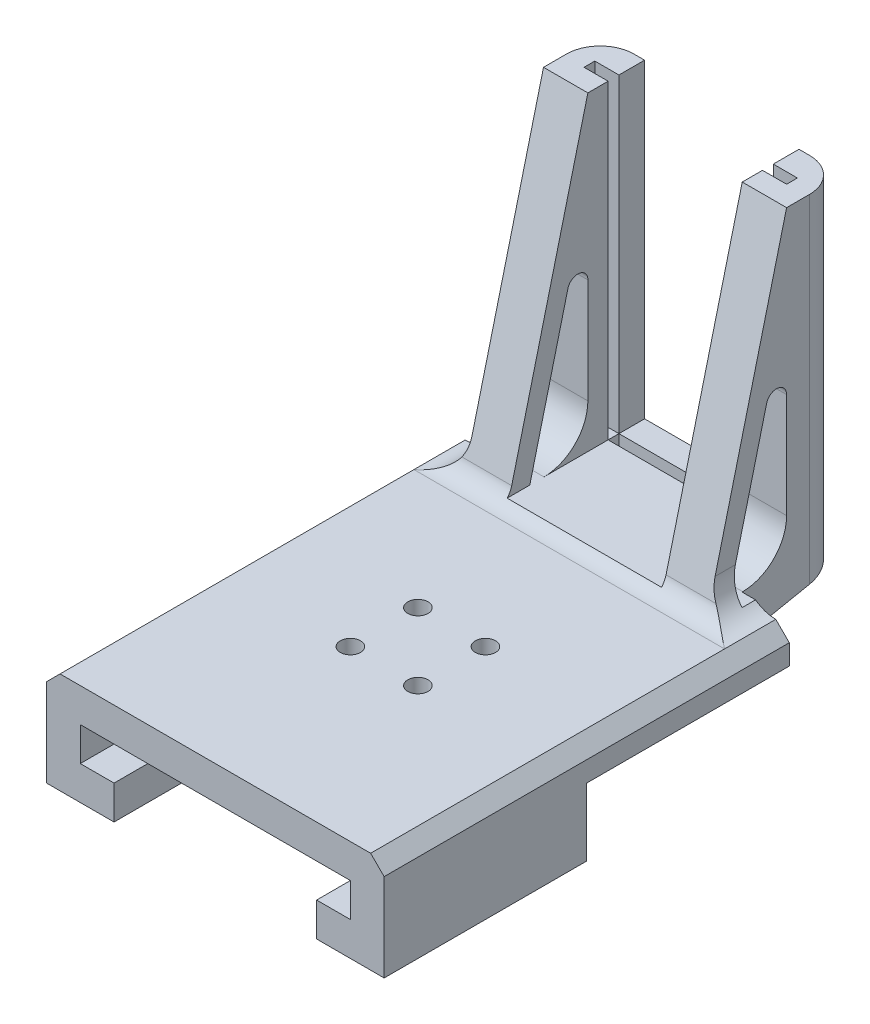
SolidWorks part; units mm, degrees
material "9400A光敏树脂"
ref_plane "前视基准面" through (0, 0, 0) normal (0, 0, 1) x (1, 0, 0)
ref_plane "上视基准面" through (0, 0, 0) normal (0, 1, 0) x (1, 0, 0)
ref_plane "右视基准面" through (0, 0, 0) normal (1, 0, 0) x (0, 0, -1)
other "Configuration Table"
sketch "草图2" plane through (0, 0, 0) normal (0, 1, 0) x (1, 0, 0)
  line L1 (-30, 30) -> (30, 30)
  line L2 (-30, 30) -> (-30, -30)
  line L3 (-30, -30) -> (30, -30)
  line L4 (30, 30) -> (30, -30)
  line L5 (-30, 30) -> (30, -30) construction
  line L6 (-30, -30) -> (30, 30) construction
  point P0 (0, 0)
  dimension "D1" = 60
  dimension "D2" = 60
extrude "凸台-拉伸1" add sketch "草图2" along normal blind 3
sketch "草图3" plane through (0, 0, 0) normal (0, 1, 0) x (1, 0, 0)
  line L1 (-5, 5) -> (5, 5) construction
  line L2 (-5, 5) -> (-5, -5) construction
  line L3 (-5, -5) -> (5, -5) construction
  line L4 (5, 5) -> (5, -5) construction
  line L5 (-5, 5) -> (5, -5) construction
  line L6 (-5, -5) -> (5, 5) construction
  circle A0 centre (-5, -5) radius 1.5
  circle A1 centre (5, -5) radius 1.5
  circle A2 centre (5, 5) radius 1.5
  circle A3 centre (-5, 5) radius 1.5
  point P0 (0, 0)
  dimension "D3" = 3
  dimension "D4" = 3
  dimension "D5" = 3
  dimension "D6" = 3
  dimension "D1" = 10
  dimension "D2" = 10
extrude "切除-拉伸1" cut sketch "草图3" along normal up to surface (3 mm away) from surface at 0 up to face at (0, 3, 0) starting at face at (0, 0, 0)
sketch "草图7" plane through (0, 0, 0) normal (0, 0, 1) x (1, 0, 0)
  line L0 (0, -1000) -> (0, 49000) construction
  line L1 (-25, 0) -> (-25, -10)
  line L2 (-30, 0) -> (30, 0) construction
  line L3 (-25, -10) -> (-15, -10)
  line L4 (-15, -10) -> (-15, -5)
  line L5 (-15, -5) -> (-20, -5)
  line L6 (-20, -5) -> (-20, 0)
  line L7 (-20, 0) -> (-25, 0)
  line L8 (-30, 3) -> (-30, 0) construction
  line L9 (20, 0) -> (25, 0)
  line L10 (20, -5) -> (20, 0)
  line L11 (15, -5) -> (20, -5)
  line L12 (15, -10) -> (15, -5)
  line L13 (25, -10) -> (15, -10)
  line L14 (25, 0) -> (25, -10)
  dimension "D1" = 5
  dimension "D2" = 5
  dimension "D3" = 10
  dimension "D4" = 5
  dimension "D5" = 5
extrude "凸台-拉伸3" add sketch "草图7" against normal blind 30 from surface at 30 starting at face at (0, 1.5, 30)
sketch "草图8" plane through (0, 0, 0) normal (0, 1, 0) x (1, 0, 0)
  line L0 (0, -1000) -> (0, 49000) construction
  line L1 (-18, 25) -> (18, 25)
  line L2 (18, 25) -> (18, 45)
  line L3 (18, 45) -> (-18, 45)
  line L4 (-18, 45) -> (-18, 25)
  line L5 (30, 30) -> (-30, 30) construction
  point P7 (0, 25)
  dimension "D1" = 36
  dimension "D2" = 20
  dimension "D3" = 5
extrude "凸台-拉伸4" add sketch "草图8" along normal blind 3 from surface at 3 starting at face at (-5, 3, -3.5)
sketch "草图10" plane through (0, 0, 0) normal (0, 1, 0) x (1, 0, 0)
  line L0 (-18, 45) -> (18, 45) construction
  line L1 (-11.43, 41.2) -> (11.43, 41.2)
  line L2 (-11.43, 41.2) -> (-11.43, 39.6)
  line L3 (-11.43, 39.6) -> (11.43, 39.6)
  line L4 (11.43, 41.2) -> (11.43, 39.6)
  point P6 (0, 45)
  point P7 (0, 41.2)
  dimension "D1" = 3.8
  dimension "D2" = 1.6
  dimension "D3" = 22.86
extrude "切除-拉伸2" cut sketch "草图10" against normal up to surface (3 mm away) from surface at 6 up to face at (0, 3, -37.5) starting at face at (0, 6, -35)
sketch "草图11" plane through (0, 0, 0) normal (0, 1, 0) x (1, 0, 0)
  line L0 (0, -1000) -> (0, 49000) construction
  line L1 (18, 41.2) -> (15, 41.2) construction
  line L2 (18, 45) -> (18, 25) construction
  line L3 (11.43, 41.2) -> (-11.43, 41.2) construction
  line L4 (11.43, 41.2) -> (11.43, 45)
  line L5 (-18, 45) -> (18, 45) construction
  line L6 (11.43, 45) -> (18, 45)
  line L7 (15, 39.6) -> (18, 39.6) construction
  line L8 (-11.43, 39.6) -> (11.43, 39.6) construction
  line L9 (18, 45) -> (18, 36.6)
  line L10 (18, 36.6) -> (11.43, 36.6)
  line L11 (11.43, 36.6) -> (11.43, 39.6)
  line L12 (11.43, 39.6) -> (15, 39.6)
  line L13 (11.43, 41.2) -> (15, 41.2)
  line L14 (15, 41.2) -> (15, 39.6)
  line L15 (-15, 39.6) -> (-18, 39.6) construction
  line L16 (-18, 41.2) -> (-15, 41.2) construction
  line L17 (-15, 41.2) -> (-15, 39.6)
  line L18 (-11.43, 41.2) -> (-15, 41.2)
  line L19 (-11.43, 39.6) -> (-15, 39.6)
  line L20 (-11.43, 36.6) -> (-11.43, 39.6)
  line L21 (-18, 36.6) -> (-11.43, 36.6)
  line L22 (-18, 45) -> (-18, 36.6)
  line L23 (-11.43, 45) -> (-18, 45)
  line L24 (-11.43, 41.2) -> (-11.43, 45)
  dimension "D1" = 3
  dimension "D2" = 3
  dimension "D3" = 3
extrude "凸台-拉伸5" add sketch "草图11" along normal blind 46 from surface at 6 starting at face at (0, 6, -40.4)
sketch "草图12" plane through (0, 0, 0) normal (1, 0, 0) x (0, 0, -1)
  line L0 (30, 0) -> (35, 3)
  line L1 (45, 3) -> (30, 3) construction
  line L2 (35, 3) -> (30, 3)
  line L3 (30, 3) -> (30, 0) construction
  line L4 (30, 3) -> (30, 0)
  dimension "D1" = 5
extrude "凸台-拉伸6" add sketch "草图12" along normal up to surface (36 mm away) from surface at -18 up to face at (18, 17.8571, -34.7429) starting at face at (-18, 17.8571, -34.7429)
sketch "草图13" plane through (0, 0, 0) normal (1, 0, 0) x (0, 0, -1)
  line L0 (25, 6) -> (36.6, 52)
  line L1 (25, 6) -> (28, 6)
  line L2 (36.6, 40.1034) -> (36.6, 52)
  line L3 (28, 6) -> (36.6, 40.1034)
  dimension "D1" = 3
extrude "凸台-拉伸8" add sketch "草图13" against normal up to surface (6.57 mm away) from surface at 18 up to face at (11.43, 29, -43.1) starting at face at (18, 14.2222, -34.2444)
sketch "草图14" plane through (0, 0, 0) normal (1, 0, 0) x (0, 0, -1)
  line L4 (36.6, 52) -> (25, 6)
  line L5 (36.6, 40.1034) -> (36.6, 52)
  line L6 (28, 6) -> (36.6, 40.1034)
  line L7 (25, 6) -> (28, 6)
  line L8 (36.6, 52) -> (25, 6)
  line L9 (36.6, 40.1034) -> (36.6, 52)
  line L10 (28, 6) -> (36.6, 40.1034)
  line L11 (25, 6) -> (28, 6)
  dimension "D1" = 0
extrude "凸台-拉伸9" add sketch "草图14" against normal up to surface (6.57 mm away) from surface at -11.43 up to face at (-18, 14.2222, -34.2444) starting at face at (-11.43, 29, -43.1)
sketch "草图15" plane through (0, 0, 0) normal (1, 0, 0) x (0, 0, -1)
  line L0 (25, 3) -> (24.2435, 3)
  line L1 (-30, 3) -> (30, 3) construction
  line L2 (24.2435, 3) -> (25, 6)
  line L3 (25, 6) -> (25, 3)
  line L4 (25, 6) -> (36.6, 52) construction
extrude "凸台-拉伸10" add sketch "草图15" against normal up to surface (36 mm away) from surface
sketch "草图16" plane through (0, 0, 0) normal (0, 1, 0) x (1, 0, 0)
  line L1 (25, -30) -> (30, -30)
  line L2 (25, -30) -> (25, 30)
  line L3 (25, 30) -> (30, 30)
  line L4 (30, -30) -> (30, 30)
  line L5 (-25, -30) -> (-30, -30)
  line L6 (-25, -30) -> (-25, 30)
  line L7 (-25, 30) -> (-30, 30)
  line L8 (-30, -30) -> (-30, 30)
extrude "切除-拉伸3" cut sketch "草图16" along normal up to surface (3 mm away) from surface at 0 up to face at (0, 3, -13.5609) starting at face at (-5, 0, 6.5)
sketch "草图17" plane through (0, 0, 0) normal (1, 0, 0) x (0, 0, -1)
  line L0 (30, 0) -> (45, 3)
  line L1 (45, 3) -> (30, 3)
  line L2 (30, 3) -> (30, 0)
extrude "凸台-拉伸11" add sketch "草图17" against normal blind 4 from surface at 18 starting at face at (18, 16.5714, -35.1205)
sketch "草图18" plane through (0, 0, 0) normal (1, 0, 0) x (0, 0, -1)
  line L0 (30, 0) -> (30, 3)
  line L1 (30, 3) -> (45, 3)
  line L2 (45, 3) -> (30, 0)
extrude "凸台-拉伸12" add sketch "草图18" along normal blind 4 from surface at -18 starting at face at (-18, 17.3678, -33.7333)
fillet "圆角3" radius 5 2 edges at (-18, 27.5, -45) (18, 27.5, -45)
fillet "圆角4" radius 10 1 edges at (0, 3, -35)
sketch "草图22" plane through (0, 0, 0) normal (0, 0, 1) x (1, 0, 0)
  line L1 (25, 3) -> (-25, 3)
  line L2 (25, 3) -> (25, 5)
  line L3 (25, 5) -> (-25, 5)
  line L4 (-25, 3) -> (-25, 5)
  dimension "D1" = 50
  dimension "D2" = 2
extrude "凸台-拉伸14" add sketch "草图22" against normal up to surface (60 mm away) from surface at 30 up to face at (-21.5, 1.5, -30) starting at face at (0, -4.5, 30)
sketch "草图24" plane through (0, 0, 0) normal (0, 0, 1) x (1, 0, 0)
  line L0 (-25, 5) -> (-23, 5)
  line L1 (25, 5) -> (-25, 5) construction
  line L2 (-23, 5) -> (-25, 3)
  line L3 (-25, 5) -> (-25, -10) construction
  line L4 (-25, 3) -> (-25, 5)
  line L5 (25, 5) -> (25, 3)
  line L6 (25, -10) -> (25, 5) construction
  line L7 (25, 3) -> (23, 5)
  line L8 (23, 5) -> (25, 5)
  dimension "D1" = 2
  dimension "D2" = 2
  dimension "D3" = 2
  dimension "D4" = 2
extrude "切除-拉伸4" cut sketch "草图24" against normal up to surface (60 mm away) from surface at 30 up to face at (-21.5, 2.5, -30) starting at face at (0, -4.1667, 30)
sketch "草图25" plane through (0, 0, 0) normal (0, 1, 0) x (1, 0, 0)
  circle A1 centre (-5, 5) radius 1.5
  circle A2 centre (-5, 5) radius 1.5
  circle A3 centre (5, 5) radius 1.5
  circle A4 centre (5, 5) radius 1.5
  circle A5 centre (5, -5) radius 1.5
  circle A6 centre (5, -5) radius 1.5
  circle A7 centre (-5, -5) radius 1.5
  circle A8 centre (-5, -5) radius 1.5
  dimension "D1" = 0
  dimension "D2" = 0
  dimension "D3" = 0
  dimension "D4" = 0
extrude "切除-拉伸5" cut sketch "草图25" against normal up to surface (5 mm away) from surface at 5 up to face at (-5, 0, 6.5) starting at face at (0, 5, -13.687)
sketch "草图26" plane through (0, 0, 0) normal (0, 1, 0) x (1, 0, 0)
  circle A0 centre (0, 0) radius 12.5
  dimension "D1" = 25
extrude "切除-拉伸6" cut sketch "草图26" along normal blind 2 from surface at 0 starting at face at (-5, 0, 6.5)
fillet "圆角5" radius 3 1 edges at (0, 0, 12.5)
fillet "圆角7" radius 5 2 edges at (-18, 5, -27.3739) (18, 5, -27.3739)
fillet "圆角8" radius 6.5 2 edges at (14.715, 6, -36.6) (-14.715, 6, -36.6)
fillet "圆角9" radius 1.5 2 edges at (-14.715, 40.1034, -36.6) (14.715, 40.1034, -36.6)
fillet "圆角10" radius 3 1 edges at (0, 5, -24.7478)
